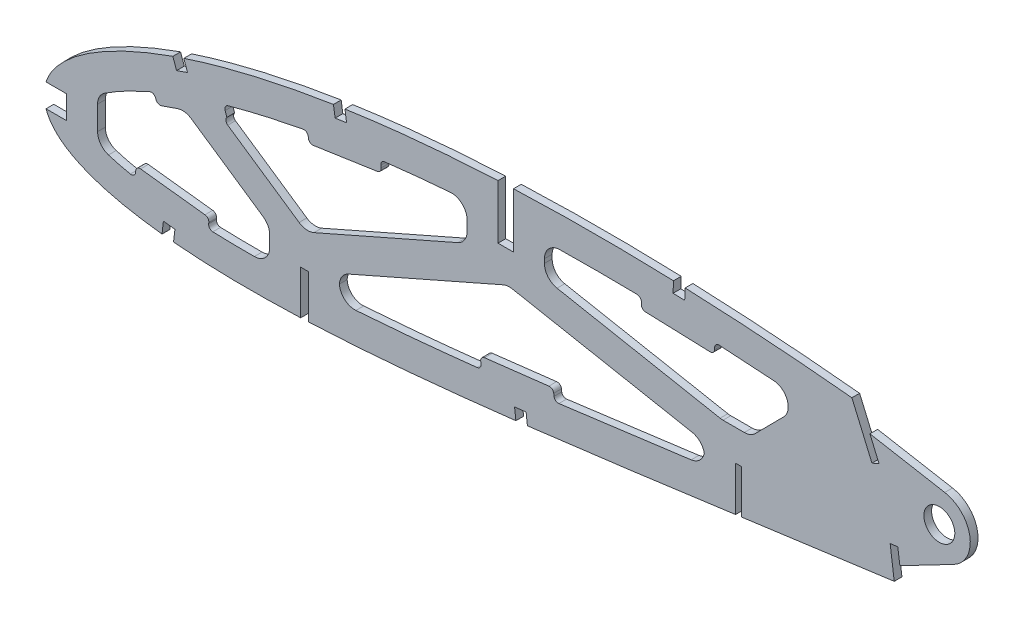
SolidWorks part; units mm, degrees
material "Pine"
ref_plane "Front Plane" through (0, 0, 0) normal (0, 0, 1) x (1, 0, 0)
ref_plane "Top Plane" through (0, 0, 0) normal (0, 1, 0) x (1, 0, 0)
ref_plane "Right Plane" through (0, 0, 0) normal (1, 0, 0) x (0, 0, -1)
curve "Curve2"
  spline degree 3 poles (520.229, 0.8111, 0) (520.1892, 0.8357, 0) (520.0299, 0.9341, 0) (519.6711, 1.1542, 0) (519.0735, 1.5208, 0) (518.237, 2.0313, 0) (517.1622, 2.6844, 0) (515.8486, 3.4756, 0) (514.2969, 4.4021, 0) (512.5075, 5.4598, 0) (510.4807, 6.6436, 0) (508.2172, 7.9486, 0) (505.7172, 9.3676, 0) (502.9816, 10.8948, 0) (500.0114, 12.5227, 0) (496.8072, 14.2443, 0) (493.3701, 16.0505, 0) (489.7015, 17.9338, 0) (485.8019, 19.8836, 0) (481.6733, 21.8919, 0) (477.317, 23.9487, 0) (472.7345, 26.0429, 0) (467.9284, 28.1661, 0) (462.9001, 30.305, 0) (457.6524, 32.4505, 0) (452.1876, 34.5902, 0) (446.5089, 36.7144, 0) (440.6184, 38.8094, 0) (434.5207, 40.866, 0) (428.2186, 42.8708, 0) (421.7166, 44.813, 0) (415.0186, 46.68, 0) (408.1302, 48.4622, 0) (401.0555, 50.1466, 0) (393.8008, 51.7219, 0) (386.3718, 53.1787, 0) (378.7746, 54.5024, 0) (371.0303, 55.692, 0) (363.2636, 56.6815, 0) (355.5128, 57.652, 0) (347.7736, 58.5637, 0) (339.9398, 59.4368, 0) (332.019, 60.2663, 0) (324.019, 61.0497, 0) (315.9478, 61.7836, 0) (307.814, 62.4658, 0) (299.6253, 63.0925, 0) (291.3904, 63.6628, 0) (283.1174, 64.1714, 0) (274.8152, 64.6183, 0) (266.4922, 65.0001, 0) (258.157, 65.3142, 0) (249.8185, 65.5589, 0) (241.4854, 65.7316, 0) (233.1666, 65.8314, 0) (224.8708, 65.8555, 0) (216.6071, 65.8035, 0) (208.384, 65.6736, 0) (200.2107, 65.464, 0) (192.0958, 65.1743, 0) (184.048, 64.8046, 0) (176.0762, 64.3519, 0) (168.189, 63.8191, 0) (160.3952, 63.2038, 0) (152.7034, 62.506, 0) (145.1216, 61.7286, 0) (137.6583, 60.8693, 0) (130.3214, 59.9308, 0) (123.1191, 58.9147, 0) (116.0593, 57.8206, 0) (109.1496, 56.6517, 0) (102.3976, 55.409, 0) (95.8102, 54.0963, 0) (89.3948, 52.714, 0) (83.1581, 51.266, 0) (77.1065, 49.7551, 0) (71.2467, 48.1838, 0) (65.5845, 46.5561, 0) (60.1256, 44.8756, 0) (54.8764, 43.1442, 0) (49.8409, 41.3683, 0) (45.0253, 39.5493, 0) (40.4333, 37.6928, 0) (36.0702, 35.8014, 0) (31.9393, 33.8806, 0) (28.0452, 31.9329, 0) (24.3908, 29.9636, 0) (20.9797, 27.9757, 0) (17.8153, 25.973, 0) (14.8987, 23.9604, 0) (12.2341, 21.9394, 0) (9.8224, 19.9149, 0) (7.6651, 17.8901, 0) (5.7652, 15.8664, 0) (4.1228, 13.8473, 0) (2.7399, 11.8344, 0) (1.6168, 9.8297, 0) (0.7561, 7.8345, 0) (0.1568, 5.85, 0) (-0.1712, 3.8792, 0) (-0.2528, 1.9205, 0) (-0.0842, 0.6392, 0) (0, 0, 0) knots 0 0 0 0 0.000254 0.001015 0.002283 0.004057 0.006331 0.009105 0.012374 0.016134 0.02038 0.025106 0.030306 0.035972 0.0421 0.048678 0.055702 0.06316 0.071046 0.07935 0.088063 0.097176 0.106678 0.116562 0.126814 0.137428 0.148394 0.1597 0.171338 0.183298 0.19557 0.208144 0.221012 0.234162 0.247587 0.261277 0.275223 0.289414 0.303771 0.317689 0.331784 0.34604 0.360444 0.374983 0.38964 0.404403 0.419257 0.434187 0.449177 0.464215 0.479284 0.49437 0.509458 0.524532 0.539579 0.554583 0.56953 0.584403 0.599191 0.613877 0.628447 0.642889 0.657186 0.671326 0.685294 0.699078 0.712665 0.726043 0.739198 0.752118 0.764792 0.777208 0.789356 0.801224 0.812804 0.824083 0.835055 0.84571 0.856038 0.866034 0.875689 0.884998 0.893953 0.902553 0.910789 0.918661 0.926166 0.933303 0.940071 0.946475 0.952518 0.958205 0.963547 0.968557 0.97325 0.977651 0.981787 0.985694 0.989415 0.993001 0.996508 1 1 1 1
curve "Curve3"
  spline degree 3 poles (0, 0, 0) (0.1336, -0.6306, 0) (0.4014, -1.8948, 0) (1.129, -3.7148, 0) (2.0912, -5.4642, 0) (3.3081, -7.1386, 0) (4.7718, -8.7374, 0) (6.479, -10.2623, 0) (8.428, -11.7125, 0) (10.6162, -13.0874, 0) (13.0406, -14.3883, 0) (15.6982, -15.6145, 0) (18.5868, -16.7656, 0) (21.7032, -17.8401, 0) (25.0435, -18.8396, 0) (28.6046, -19.7616, 0) (32.3825, -20.6074, 0) (36.3735, -21.375, 0) (40.5732, -22.065, 0) (44.9774, -22.6771, 0) (49.5814, -23.2117, 0) (54.3808, -23.6676, 0) (59.3708, -24.0458, 0) (64.5464, -24.3466, 0) (69.9027, -24.5709, 0) (75.4344, -24.718, 0) (81.1363, -24.7899, 0) (87.003, -24.788, 0) (93.0289, -24.7115, 0) (99.2088, -24.5648, 0) (105.5368, -24.3469, 0) (112.0073, -24.0604, 0) (118.6142, -23.7083, 0) (125.3518, -23.2917, 0) (132.2141, -22.8125, 0) (139.1951, -22.2745, 0) (146.2885, -21.679, 0) (153.4882, -21.0296, 0) (160.7876, -20.3295, 0) (168.1806, -19.5808, 0) (175.6606, -18.7872, 0) (183.2209, -17.9512, 0) (190.8551, -17.0772, 0) (198.5563, -16.1668, 0) (206.3179, -15.2253, 0) (214.1326, -14.2544, 0) (221.9939, -13.2579, 0) (229.8947, -12.2404, 0) (237.8276, -11.2019, 0) (245.786, -10.1497, 0) (253.7621, -9.0829, 0) (261.7491, -8.0072, 0) (269.7395, -6.9257, 0) (277.7256, -5.8389, 0) (285.7003, -4.7513, 0) (293.6562, -3.6657, 0) (301.5856, -2.5824, 0) (309.4812, -1.5067, 0) (317.3352, -0.4385, 0) (325.1402, 0.6201, 0) (332.8888, 1.6659, 0) (340.5737, 2.6975, 0) (348.187, 3.7144, 0) (355.721, 4.7168, 0) (363.0553, 5.6745, 0) (370.1707, 6.6383, 0) (377.0913, 7.4284, 0) (383.9258, 8.1028, 0) (390.6811, 8.6557, 0) (397.3493, 9.0951, 0) (403.9227, 9.4241, 0) (410.3934, 9.6473, 0) (416.7532, 9.7713, 0) (422.9943, 9.7993, 0) (429.1081, 9.7402, 0) (435.0867, 9.5987, 0) (440.9216, 9.3813, 0) (446.6049, 9.0952, 0) (452.1283, 8.7483, 0) (457.4837, 8.3456, 0) (462.6634, 7.8966, 0) (467.6597, 7.4078, 0) (472.4647, 6.8849, 0) (477.0715, 6.3387, 0) (481.4727, 5.7729, 0) (485.6616, 5.1968, 0) (489.6316, 4.6162, 0) (493.3764, 4.0385, 0) (496.89, 3.4693, 0) (500.1667, 2.916, 0) (503.2016, 2.384, 0) (505.9892, 1.8782, 0) (508.5257, 1.4052, 0) (510.8062, 0.9673, 0) (512.8275, 0.5717, 0) (514.5859, 0.2202, 0) (516.0789, -0.0824, 0) (517.3037, -0.3347, 0) (518.2586, -0.5328, 0) (518.9417, -0.6767, 0) (519.3522, -0.7624, 0) (519.5346, -0.8013, 0) (519.5802, -0.8111, 0) knots 0 0 0 0 0.003638 0.007293 0.011028 0.014901 0.018963 0.023258 0.027821 0.032679 0.037853 0.043362 0.049215 0.055422 0.061989 0.068918 0.076211 0.083868 0.091887 0.100266 0.109 0.118085 0.127515 0.137285 0.147388 0.157816 0.168563 0.179619 0.190977 0.202627 0.21456 0.226767 0.239236 0.251959 0.264924 0.27812 0.291536 0.30516 0.318981 0.332985 0.347163 0.361499 0.375981 0.390597 0.405333 0.420175 0.43511 0.450124 0.465203 0.480333 0.495501 0.51069 0.525887 0.541078 0.556247 0.571382 0.586466 0.601485 0.616424 0.631269 0.646007 0.660621 0.675098 0.689423 0.703582 0.716908 0.730009 0.742952 0.755726 0.76832 0.780724 0.792927 0.804916 0.816679 0.828204 0.839475 0.850481 0.861208 0.871639 0.881763 0.891564 0.901027 0.910139 0.918884 0.927249 0.935221 0.942785 0.949928 0.956638 0.962904 0.968712 0.974054 0.978918 0.983297 0.98718 0.990561 0.993433 0.995791 0.99763 0.998946 0.999737 1 1 1 1
sketch "Sketch1" plane through (0, 0, 0) normal (0, 0, 1) x (1, 0, 0)
  line L1 (519.5802, -0.8111) -> (524.4049, -1.7687)
  line L2 (520.229, 0.8111) -> (524.4049, -1.7687)
  spline S0 degree 3 poles (-2903.7635, -749.124) (66.2436, 68.8235) (-8.6937, 20.855) (1.129, -3.7148) (2.0912, -5.4642) (3.3081, -7.1386) (4.7718, -8.7374) (6.479, -10.2623) (8.428, -11.7125) (10.6162, -13.0874) (13.0406, -14.3883) (15.6982, -15.6145) (18.5868, -16.7656) (21.7032, -17.8401) (25.0435, -18.8396) (28.6046, -19.7616) (32.3825, -20.6074) (36.3735, -21.375) (40.5732, -22.065) (44.9774, -22.6771) (49.5814, -23.2117) (54.3808, -23.6676) (59.3708, -24.0458) (64.5464, -24.3466) (69.9027, -24.5709) (75.4344, -24.718) (81.1363, -24.7899) (87.003, -24.788) (93.0289, -24.7115) (99.2088, -24.5648) (105.5368, -24.3469) (112.0073, -24.0604) (118.6142, -23.7083) (125.3518, -23.2917) (132.2141, -22.8125) (139.1951, -22.2745) (146.2885, -21.679) (153.4882, -21.0296) (160.7876, -20.3295) (168.1806, -19.5808) (175.6606, -18.7872) (183.2209, -17.9512) (190.8551, -17.0772) (198.5563, -16.1668) (206.3179, -15.2253) (214.1326, -14.2544) (221.9939, -13.2579) (229.8947, -12.2404) (237.8276, -11.2019) (245.786, -10.1497) (253.7621, -9.0829) (261.7491, -8.0072) (269.7395, -6.9257) (277.7256, -5.8389) (285.7003, -4.7513) (293.6562, -3.6657) (301.5856, -2.5824) (309.4812, -1.5067) (317.3352, -0.4385) (325.1402, 0.6201) (332.8888, 1.6659) (340.5737, 2.6975) (348.187, 3.7144) (355.721, 4.7168) (363.0553, 5.6745) (370.1707, 6.6383) (377.0913, 7.4284) (383.9258, 8.1028) (390.6811, 8.6557) (397.3493, 9.0951) (403.9227, 9.4241) (410.3934, 9.6473) (416.7532, 9.7713) (422.9943, 9.7993) (429.1081, 9.7402) (435.0867, 9.5987) (440.9216, 9.3813) (446.6049, 9.0952) (452.1283, 8.7483) (457.4837, 8.3456) (462.6634, 7.8966) (467.6597, 7.4078) (472.4647, 6.8849) (477.0715, 6.3387) (481.4727, 5.7729) (485.6616, 5.1968) (489.6316, 4.6162) (493.3764, 4.0385) (496.89, 3.4693) (500.1667, 2.916) (503.2016, 2.384) (505.9892, 1.8782) (508.5257, 1.4052) (510.8062, 0.9673) (512.8275, 0.5717) (514.5859, 0.2202) (516.0789, -0.0824) (517.3037, -0.3347) (518.2586, -0.5328) (518.9417, -0.6767) (537.0698, -4.4604) (553.3394, -15.9066) (1193.1482, 2921.6684) knots -0.137857 -0.137857 -0.137857 -0.137857 0.003638 0.007293 0.011028 0.014901 0.018963 0.023258 0.027821 0.032679 0.037853 0.043362 0.049215 0.055422 0.061989 0.068918 0.076211 0.083868 0.091887 0.100266 0.109 0.118085 0.127515 0.137285 0.147388 0.157816 0.168563 0.179619 0.190977 0.202627 0.21456 0.226767 0.239236 0.251959 0.264924 0.27812 0.291536 0.30516 0.318981 0.332985 0.347163 0.361499 0.375981 0.390597 0.405333 0.420175 0.43511 0.450124 0.465203 0.480333 0.495501 0.51069 0.525887 0.541078 0.556247 0.571382 0.586466 0.601485 0.616424 0.631269 0.646007 0.660621 0.675098 0.689423 0.703582 0.716908 0.730009 0.742952 0.755726 0.76832 0.780724 0.792927 0.804916 0.816679 0.828204 0.839475 0.850481 0.861208 0.871639 0.881763 0.891564 0.901027 0.910139 0.918884 0.927249 0.935221 0.942785 0.949928 0.956638 0.962904 0.968712 0.974054 0.978918 0.983297 0.98718 0.990561 0.993433 0.995791 0.99763 0.998946 0.999737 1.102307 1.102307 1.102307 1.102307 only from (0, 0) to (519.5802, -0.8111) construction
  spline S1 degree 3 poles (2144.5607, 2521.6799) (550.9976, -26.3511) (537.2872, -9.6513) (519.6711, 1.1542) (519.0735, 1.5208) (518.237, 2.0313) (517.1622, 2.6844) (515.8486, 3.4756) (514.2969, 4.4021) (512.5075, 5.4598) (510.4807, 6.6436) (508.2172, 7.9486) (505.7172, 9.3676) (502.9816, 10.8948) (500.0114, 12.5227) (496.8072, 14.2443) (493.3701, 16.0505) (489.7015, 17.9338) (485.8019, 19.8836) (481.6733, 21.8919) (477.317, 23.9487) (472.7345, 26.0429) (467.9284, 28.1661) (462.9001, 30.305) (457.6524, 32.4505) (452.1876, 34.5902) (446.5089, 36.7144) (440.6184, 38.8094) (434.5207, 40.866) (428.2186, 42.8708) (421.7166, 44.813) (415.0186, 46.68) (408.1302, 48.4622) (401.0555, 50.1466) (393.8008, 51.7219) (386.3718, 53.1787) (378.7746, 54.5024) (371.0303, 55.692) (363.2636, 56.6815) (355.5128, 57.652) (347.7736, 58.5637) (339.9398, 59.4368) (332.019, 60.2663) (324.019, 61.0497) (315.9478, 61.7836) (307.814, 62.4658) (299.6253, 63.0925) (291.3904, 63.6628) (283.1174, 64.1714) (274.8152, 64.6183) (266.4922, 65.0001) (258.157, 65.3142) (249.8185, 65.5589) (241.4854, 65.7316) (233.1666, 65.8314) (224.8708, 65.8555) (216.6071, 65.8035) (208.384, 65.6736) (200.2107, 65.464) (192.0958, 65.1743) (184.048, 64.8046) (176.0762, 64.3519) (168.189, 63.8191) (160.3952, 63.2038) (152.7034, 62.506) (145.1216, 61.7286) (137.6583, 60.8693) (130.3214, 59.9308) (123.1191, 58.9147) (116.0593, 57.8206) (109.1496, 56.6517) (102.3976, 55.409) (95.8102, 54.0963) (89.3948, 52.714) (83.1581, 51.266) (77.1065, 49.7551) (71.2467, 48.1838) (65.5845, 46.5561) (60.1256, 44.8756) (54.8764, 43.1442) (49.8409, 41.3683) (45.0253, 39.5493) (40.4333, 37.6928) (36.0702, 35.8014) (31.9393, 33.8806) (28.0452, 31.9329) (24.3908, 29.9636) (20.9797, 27.9757) (17.8153, 25.973) (14.8987, 23.9604) (12.2341, 21.9394) (9.8224, 19.9149) (7.6651, 17.8901) (5.7652, 15.8664) (4.1228, 13.8473) (2.7399, 11.8344) (1.6168, 9.8297) (0.7561, 7.8345) (0.1568, 5.85) (-0.1712, 3.8792) (-1.2714, -22.5145) (85.5395, -42.7616) (-2987.8188, -259.5241) knots -0.109813 -0.109813 -0.109813 -0.109813 0.000254 0.001015 0.002283 0.004057 0.006331 0.009105 0.012374 0.016134 0.02038 0.025106 0.030306 0.035972 0.0421 0.048678 0.055702 0.06316 0.071046 0.07935 0.088063 0.097176 0.106678 0.116562 0.126814 0.137428 0.148394 0.1597 0.171338 0.183298 0.19557 0.208144 0.221012 0.234162 0.247587 0.261277 0.275223 0.289414 0.303771 0.317689 0.331784 0.34604 0.360444 0.374983 0.38964 0.404403 0.419257 0.434187 0.449177 0.464215 0.479284 0.49437 0.509458 0.524532 0.539579 0.554583 0.56953 0.584403 0.599191 0.613877 0.628447 0.642889 0.657186 0.671326 0.685294 0.699078 0.712665 0.726043 0.739198 0.752118 0.764792 0.777208 0.789356 0.801224 0.812804 0.824083 0.835055 0.84571 0.856038 0.866034 0.875689 0.884998 0.893953 0.902553 0.910789 0.918661 0.926166 0.933303 0.940071 0.946475 0.952518 0.958205 0.963547 0.968557 0.97325 0.977651 0.981787 0.985694 0.989415 0.993001 0.996508 1.132043 1.132043 1.132043 1.132043 only from (520.229, 0.8111) to (0, 0) construction
  spline S2 degree 3 poles (0, 0) (0.1336, -0.6306) (0.4014, -1.8948) (1.129, -3.7148) (2.0912, -5.4642) (3.3081, -7.1386) (4.7718, -8.7374) (6.479, -10.2623) (8.428, -11.7125) (10.6162, -13.0874) (13.0406, -14.3883) (15.6982, -15.6145) (18.5868, -16.7656) (21.7032, -17.8401) (25.0435, -18.8396) (28.6046, -19.7616) (32.3825, -20.6074) (36.3735, -21.375) (40.5732, -22.065) (44.9774, -22.6771) (49.5814, -23.2117) (54.3808, -23.6676) (59.3708, -24.0458) (64.5464, -24.3466) (69.9027, -24.5709) (75.4344, -24.718) (81.1363, -24.7899) (87.003, -24.788) (93.0289, -24.7115) (99.2088, -24.5648) (105.5368, -24.3469) (112.0073, -24.0604) (118.6142, -23.7083) (125.3518, -23.2917) (132.2141, -22.8125) (139.1951, -22.2745) (146.2885, -21.679) (153.4882, -21.0296) (160.7876, -20.3295) (168.1806, -19.5808) (175.6606, -18.7872) (183.2209, -17.9512) (190.8551, -17.0772) (198.5563, -16.1668) (206.3179, -15.2253) (214.1326, -14.2544) (221.9939, -13.2579) (229.8947, -12.2404) (237.8276, -11.2019) (245.786, -10.1497) (253.7621, -9.0829) (261.7491, -8.0072) (269.7395, -6.9257) (277.7256, -5.8389) (285.7003, -4.7513) (293.6562, -3.6657) (301.5856, -2.5824) (309.4812, -1.5067) (317.3352, -0.4385) (325.1402, 0.6201) (332.8888, 1.6659) (340.5737, 2.6975) (348.187, 3.7144) (355.721, 4.7168) (363.0553, 5.6745) (370.1707, 6.6383) (377.0913, 7.4284) (383.9258, 8.1028) (390.6811, 8.6557) (397.3493, 9.0951) (403.9227, 9.4241) (410.3934, 9.6473) (416.7532, 9.7713) (422.9943, 9.7993) (429.1081, 9.7402) (435.0867, 9.5987) (440.9216, 9.3813) (446.6049, 9.0952) (452.1283, 8.7483) (457.4837, 8.3456) (462.6634, 7.8966) (467.6597, 7.4078) (472.4647, 6.8849) (477.0715, 6.3387) (481.4727, 5.7729) (485.6616, 5.1968) (489.6316, 4.6162) (493.3764, 4.0385) (496.89, 3.4693) (500.1667, 2.916) (503.2016, 2.384) (505.9892, 1.8782) (508.5257, 1.4052) (510.8062, 0.9673) (512.8275, 0.5717) (514.5859, 0.2202) (516.0789, -0.0824) (517.3037, -0.3347) (518.2586, -0.5328) (518.9417, -0.6767) (519.3522, -0.7624) (519.5346, -0.8013) (519.5802, -0.8111) knots 0 0 0 0 0.003638 0.007293 0.011028 0.014901 0.018963 0.023258 0.027821 0.032679 0.037853 0.043362 0.049215 0.055422 0.061989 0.068918 0.076211 0.083868 0.091887 0.100266 0.109 0.118085 0.127515 0.137285 0.147388 0.157816 0.168563 0.179619 0.190977 0.202627 0.21456 0.226767 0.239236 0.251959 0.264924 0.27812 0.291536 0.30516 0.318981 0.332985 0.347163 0.361499 0.375981 0.390597 0.405333 0.420175 0.43511 0.450124 0.465203 0.480333 0.495501 0.51069 0.525887 0.541078 0.556247 0.571382 0.586466 0.601485 0.616424 0.631269 0.646007 0.660621 0.675098 0.689423 0.703582 0.716908 0.730009 0.742952 0.755726 0.76832 0.780724 0.792927 0.804916 0.816679 0.828204 0.839475 0.850481 0.861208 0.871639 0.881763 0.891564 0.901027 0.910139 0.918884 0.927249 0.935221 0.942785 0.949928 0.956638 0.962904 0.968712 0.974054 0.978918 0.983297 0.98718 0.990561 0.993433 0.995791 0.99763 0.998946 0.999737 1 1 1 1
  spline S3 degree 3 poles (520.229, 0.8111) (520.1892, 0.8357) (520.0299, 0.9341) (519.6711, 1.1542) (519.0735, 1.5208) (518.237, 2.0313) (517.1622, 2.6844) (515.8486, 3.4756) (514.2969, 4.4021) (512.5075, 5.4598) (510.4807, 6.6436) (508.2172, 7.9486) (505.7172, 9.3676) (502.9816, 10.8948) (500.0114, 12.5227) (496.8072, 14.2443) (493.3701, 16.0505) (489.7015, 17.9338) (485.8019, 19.8836) (481.6733, 21.8919) (477.317, 23.9487) (472.7345, 26.0429) (467.9284, 28.1661) (462.9001, 30.305) (457.6524, 32.4505) (452.1876, 34.5902) (446.5089, 36.7144) (440.6184, 38.8094) (434.5207, 40.866) (428.2186, 42.8708) (421.7166, 44.813) (415.0186, 46.68) (408.1302, 48.4622) (401.0555, 50.1466) (393.8008, 51.7219) (386.3718, 53.1787) (378.7746, 54.5024) (371.0303, 55.692) (363.2636, 56.6815) (355.5128, 57.652) (347.7736, 58.5637) (339.9398, 59.4368) (332.019, 60.2663) (324.019, 61.0497) (315.9478, 61.7836) (307.814, 62.4658) (299.6253, 63.0925) (291.3904, 63.6628) (283.1174, 64.1714) (274.8152, 64.6183) (266.4922, 65.0001) (258.157, 65.3142) (249.8185, 65.5589) (241.4854, 65.7316) (233.1666, 65.8314) (224.8708, 65.8555) (216.6071, 65.8035) (208.384, 65.6736) (200.2107, 65.464) (192.0958, 65.1743) (184.048, 64.8046) (176.0762, 64.3519) (168.189, 63.8191) (160.3952, 63.2038) (152.7034, 62.506) (145.1216, 61.7286) (137.6583, 60.8693) (130.3214, 59.9308) (123.1191, 58.9147) (116.0593, 57.8206) (109.1496, 56.6517) (102.3976, 55.409) (95.8102, 54.0963) (89.3948, 52.714) (83.1581, 51.266) (77.1065, 49.7551) (71.2467, 48.1838) (65.5845, 46.5561) (60.1256, 44.8756) (54.8764, 43.1442) (49.8409, 41.3683) (45.0253, 39.5493) (40.4333, 37.6928) (36.0702, 35.8014) (31.9393, 33.8806) (28.0452, 31.9329) (24.3908, 29.9636) (20.9797, 27.9757) (17.8153, 25.973) (14.8987, 23.9604) (12.2341, 21.9394) (9.8224, 19.9149) (7.6651, 17.8901) (5.7652, 15.8664) (4.1228, 13.8473) (2.7399, 11.8344) (1.6168, 9.8297) (0.7561, 7.8345) (0.1568, 5.85) (-0.1712, 3.8792) (-0.2528, 1.9205) (-0.0842, 0.6392) (0, 0) knots 0 0 0 0 0.000254 0.001015 0.002283 0.004057 0.006331 0.009105 0.012374 0.016134 0.02038 0.025106 0.030306 0.035972 0.0421 0.048678 0.055702 0.06316 0.071046 0.07935 0.088063 0.097176 0.106678 0.116562 0.126814 0.137428 0.148394 0.1597 0.171338 0.183298 0.19557 0.208144 0.221012 0.234162 0.247587 0.261277 0.275223 0.289414 0.303771 0.317689 0.331784 0.34604 0.360444 0.374983 0.38964 0.404403 0.419257 0.434187 0.449177 0.464215 0.479284 0.49437 0.509458 0.524532 0.539579 0.554583 0.56953 0.584403 0.599191 0.613877 0.628447 0.642889 0.657186 0.671326 0.685294 0.699078 0.712665 0.726043 0.739198 0.752118 0.764792 0.777208 0.789356 0.801224 0.812804 0.824083 0.835055 0.84571 0.856038 0.866034 0.875689 0.884998 0.893953 0.902553 0.910789 0.918661 0.926166 0.933303 0.940071 0.946475 0.952518 0.958205 0.963547 0.968557 0.97325 0.977651 0.981787 0.985694 0.989415 0.993001 0.996508 1 1 1 1
extrude "Boss-Extrude1" add sketch "Sketch1" along normal blind 3.175
sketch "Sketch2" plane through (0, 0, 0) normal (0, 0, -1) x (-1, 0, 0)
  line L2 (-286.0676, 13.2177) -> (-286.0676, -4.8021)
  line L7 (-192.4051, 65.2789) -> (-192.4051, 42.658)
  line L10 (-108.2676, -6.3385) -> (-108.2676, -24.0465)
  line L14 (-283.5276, 13.2177) -> (-283.5276, -4.8021)
  line L19 (-186.0551, 65.2789) -> (-186.0551, 42.658)
  line L22 (-105.0926, -6.3385) -> (-105.0926, -24.0465)
  line L24 (-286.0676, -4.8021) -> (-286.0676, -8.3904)
  line L25 (-286.0676, -8.3904) -> (-283.5276, -6.5962)
  line L26 (-283.5276, -6.5962) -> (-283.5276, -4.8021)
  line L27 (-192.4051, 65.2789) -> (-192.4051, 74.5745)
  line L28 (-192.4051, 74.5745) -> (-186.0551, 68.2245)
  line L29 (-186.0551, 68.2245) -> (-186.0551, 65.2789)
  line L30 (-108.2676, -24.0465) -> (-108.2676, -27.6366)
  line L31 (-108.2676, -27.6366) -> (-105.0926, -25.3939)
  line L32 (-105.0926, -25.3939) -> (-105.0926, -24.0465)
  line L33 (-108.2676, -6.3385) -> (-105.0926, -6.3385)
  line L34 (-192.4051, 42.658) -> (-186.0551, 42.658)
  line L35 (-286.0676, 13.2177) -> (-283.5276, 13.2177)
extrude "Cut-Extrude2" cut sketch "Sketch2" against normal blind 7.62
sketch "Sketch4" plane through (0, 0, 0) normal (0, 0, -1) x (-1, 0, 0)
  circle A1 centre (-367.1422, 33.2326) radius 6.35
extrude "Cut-Extrude3" cut sketch "Sketch4" against normal blind 7.62
sketch "Sketch5" plane through (0, 0, 0) normal (0, 0, -1) x (-1, 0, 0)
  line L0 (-348.2218, 35.451) -> (-350.8885, 58.1944) construction
  line L1 (-350.8885, 58.1944) -> (-391.6719, 53.4125) construction
  line L2 (-348.2581, 30.7238) -> (-350.9465, 10.4871) construction
  line L3 (-351.7828, 4.1924) -> (-398.5601, 10.4067) construction
  line L4 (-367.1422, 33.2326) -> (-348.2218, 35.451) construction
  line L5 (-367.1422, 33.2326) -> (-349.6474, 25.6936) construction
  line L6 (-349.6474, 25.6936) -> (-338.6489, 51.2166) construction
  line L7 (-338.6489, 51.2166) -> (-342.4184, 42.4692)
  line L9 (-342.4184, 42.4692) -> (-339.5026, 41.2127)
  line L10 (-331.9636, 58.7075) -> (-339.5026, 41.2127)
  line L11 (-350.9465, 10.4871) -> (-350.1103, 16.7818)
  line L13 (-350.1103, 16.7818) -> (-346.9629, 16.3637)
  line L14 (-348.6354, 3.7743) -> (-346.9629, 16.3637)
  line L15 (-373.0051, 21.9669) -> (-350.9465, 10.4871)
  line L16 (-369.3728, 45.7352) -> (-338.6489, 51.2166)
  line L17 (-331.9636, 58.7075) -> (-329.4445, 64.5532)
  line L18 (-329.4445, 64.5532) -> (-547.4475, 21.9669)
  line L19 (-547.4475, 21.9669) -> (-524.2073, -22.3113)
  line L20 (-524.2073, -22.3113) -> (-348.6354, 3.7743)
  circle A2 centre (-367.1422, 33.2326) radius 19.05
  circle A3 centre (-367.1422, 33.2326) radius 19.05 construction
  circle A4 centre (-367.1422, 33.2326) radius 12.7
  arc A5 (-369.3728, 45.7352) -> (-373.0051, 21.9669) centre (-367.1422, 33.2326) ccw
  spline S0 degree 3 poles (-520.229, 0.8111) (-520.1892, 0.8357) (-520.0299, 0.9341) (-519.6711, 1.1542) (-519.0735, 1.5208) (-518.237, 2.0313) (-517.1622, 2.6844) (-515.8486, 3.4756) (-514.2969, 4.4021) (-512.5075, 5.4598) (-510.4807, 6.6436) (-508.2172, 7.9486) (-505.7172, 9.3676) (-502.9816, 10.8948) (-500.0114, 12.5227) (-496.8072, 14.2443) (-493.3701, 16.0505) (-489.7015, 17.9338) (-485.8019, 19.8836) (-481.6733, 21.8919) (-477.317, 23.9487) (-472.7345, 26.0429) (-467.9284, 28.1661) (-462.9001, 30.305) (-457.6524, 32.4505) (-452.1876, 34.5902) (-446.5089, 36.7144) (-440.6184, 38.8094) (-434.5207, 40.866) (-428.2186, 42.8708) (-421.7166, 44.813) (-415.0186, 46.68) (-408.1302, 48.4622) (-401.0555, 50.1466) (-393.8008, 51.7219) (-386.3718, 53.1787) (-378.7746, 54.5024) (-371.0303, 55.692) (-363.2636, 56.6815) (-355.5128, 57.652) (-347.7736, 58.5637) (-339.9398, 59.4368) (-332.019, 60.2663) (-324.019, 61.0497) (-315.9478, 61.7836) (-307.814, 62.4658) (-299.6253, 63.0925) (-291.3904, 63.6628) (-283.1174, 64.1714) (-274.8152, 64.6183) (-266.4922, 65.0001) (-258.157, 65.3142) (-249.8185, 65.5589) (-241.4854, 65.7316) (-233.1666, 65.8314) (-224.8708, 65.8555) (-216.6071, 65.8035) (-208.384, 65.6736) (-200.3208, 65.4668) (-195.0004, 65.2779) (-192.4051, 65.1731) knots 0 0 0 0 0.000254 0.001015 0.002283 0.004057 0.006331 0.009105 0.012374 0.016134 0.02038 0.025106 0.030306 0.035972 0.0421 0.048678 0.055702 0.06316 0.071046 0.07935 0.088063 0.097176 0.106678 0.116562 0.126814 0.137428 0.148394 0.1597 0.171338 0.183298 0.19557 0.208144 0.221012 0.234162 0.247587 0.261277 0.275223 0.289414 0.303771 0.317689 0.331784 0.34604 0.360444 0.374983 0.38964 0.404403 0.419257 0.434187 0.449177 0.464215 0.479284 0.49437 0.509458 0.524532 0.539579 0.554583 0.56953 0.584403 0.599191 0.61328 0.61328 0.61328 0.61328 construction
  spline S1 degree 3 poles (-286.0676, -4.7011) (-288.6001, -4.3556) (-293.7767, -3.6493) (-301.5856, -2.5824) (-309.4812, -1.5067) (-317.3352, -0.4385) (-325.1402, 0.6201) (-332.8888, 1.6659) (-340.5737, 2.6975) (-348.187, 3.7144) (-355.721, 4.7168) (-363.0553, 5.6745) (-370.1707, 6.6383) (-377.0913, 7.4284) (-383.9258, 8.1028) (-390.6811, 8.6557) (-397.3493, 9.0951) (-403.9227, 9.4241) (-410.3934, 9.6473) (-416.7532, 9.7713) (-422.9943, 9.7993) (-429.1081, 9.7402) (-435.0867, 9.5987) (-440.9216, 9.3813) (-446.6049, 9.0952) (-452.1283, 8.7483) (-457.4837, 8.3456) (-462.6634, 7.8966) (-467.6597, 7.4078) (-472.4647, 6.8849) (-477.0715, 6.3387) (-481.4727, 5.7729) (-485.6616, 5.1968) (-489.6316, 4.6162) (-493.3764, 4.0385) (-496.89, 3.4693) (-500.1667, 2.916) (-503.2016, 2.384) (-505.9892, 1.8782) (-508.5257, 1.4052) (-510.8062, 0.9673) (-512.8275, 0.5717) (-514.5859, 0.2202) (-516.0789, -0.0824) (-517.3037, -0.3347) (-518.2586, -0.5328) (-518.9417, -0.6767) (-519.3522, -0.7624) (-519.5346, -0.8013) (-519.5802, -0.8111) knots 0.556934 0.556934 0.556934 0.556934 0.571382 0.586466 0.601485 0.616424 0.631269 0.646007 0.660621 0.675098 0.689423 0.703582 0.716908 0.730009 0.742952 0.755726 0.76832 0.780724 0.792927 0.804916 0.816679 0.828204 0.839475 0.850481 0.861208 0.871639 0.881763 0.891564 0.901027 0.910139 0.918884 0.927249 0.935221 0.942785 0.949928 0.956638 0.962904 0.968712 0.974054 0.978918 0.983297 0.98718 0.990561 0.993433 0.995791 0.99763 0.998946 0.999737 1 1 1 1 construction
  dimension "D2" = 30
  dimension "D3" = 19.05
  dimension "D4" = 3.175
  dimension "D5" = 3.175
  dimension "D6" = 12.7
  dimension "D1" = 12.7
  dimension "D7" = 6.35
extrude "Cut-Extrude4" cut sketch "Sketch5" against normal blind 7.62
sketch "Sketch6" plane through (0, 0, 3.175) normal (0, 0, 1) x (1, 0, 0)
  line L1 (9.0491, -2.3116) -> (9.0491, 7.2134)
  line L2 (48.2015, -22.9304) -> (48.143, -23.4415)
  line L3 (-0.4759, 7.2134) -> (9.0491, 7.2134)
  line L4 (52.9259, -23.471) -> (52.8674, -23.9821)
  line L5 (58.6444, 39.5788) -> (57.0937, 44.0456)
  line L6 (48.143, -23.4415) -> (52.8674, -23.9821)
  line L7 (53.4849, -18.7224) -> (48.7591, -18.1683)
  line L9 (52.9259, -23.471) -> (53.4849, -18.7224)
  line L11 (123.9218, 54.3657) -> (123.2199, 59.0934)
  line L13 (198.1367, -16.3203) -> (197.5795, -11.5893)
  line L15 (197.5795, -11.5893) -> (192.8497, -12.1463)
  line L17 (262.6616, 60.6229) -> (262.8439, 65.3728)
  line L19 (257.9021, 60.7874) -> (262.6616, 60.6229)
  line L21 (258.0615, 65.5447) -> (257.9021, 60.7874)
  line L23 (192.8497, -12.1463) -> (193.4048, -16.8803)
  line L25 (119.2109, 53.6664) -> (123.9218, 54.3657)
  line L27 (118.502, 58.3704) -> (119.2109, 53.6664)
  line L29 (48.7591, -18.1683) -> (48.2015, -22.9304)
  line L31 (54.1454, 38.0169) -> (58.6444, 39.5788)
  line L33 (52.5867, 42.5063) -> (54.1454, 38.0169)
  line L35 (-0.4759, -2.3116) -> (9.0491, -2.3116)
  line L37 (-0.4759, -2.3116) -> (-0.4759, 7.2134)
  arc A1 (123.2199, 59.0934) -> (118.502, 58.3704) centre (443.7447, -2048.1229) ccw
  arc A3 (262.8439, 65.3728) -> (258.0615, 65.5447) centre (100.7832, -4376.4516) ccw
  arc A5 (193.4048, -16.8803) -> (198.1367, -16.3203) centre (-903.0921, 9268.763) ccw
  spline S1 degree 3 poles (57.0937, 44.0456) (56.342, 43.7907) (54.8391, 43.2792) (53.3372, 42.7645) (52.5867, 42.5063) knots 0 0 0 0 0.5 1 1 1 1
extrude "Cut-Extrude5" cut sketch "Sketch6" against normal blind 7.62
sketch "Sketch7" plane through (0, 0, 3.175) normal (0, 0, 1) x (1, 0, 0)
  line L0 (57.545, 25.7536) -> (52.3119, 23.9368)
  line L1 (92.3926, -12.01) -> (92.3926, 6.3615) construction
  line L2 (92.3926, 6.3615) -> (114.6176, 6.3615) construction
  line L3 (107.3436, 7.2399) -> (173.3551, 36.2646)
  line L4 (173.3551, 36.308) -> (173.3551, 51.4354)
  line L5 (137.6967, 48.0627) -> (138.349, 43.6684)
  line L6 (138.349, 43.6684) -> (108.5412, 39.2432)
  line L7 (108.5412, 39.2432) -> (107.899, 43.5043)
  line L8 (73.4693, 35.5995) -> (74.8069, 31.7464)
  line L9 (74.8069, 31.7464) -> (72.4953, 30.9439)
  line L10 (173.3551, 36.308) -> (173.3551, 36.2646)
  line L11 (72.4953, 30.9439) -> (107.3436, 7.2399)
  line L12 (107.3436, 7.2399) -> (186.6743, 42.1209) construction
  line L13 (62.0489, 38.0496) -> (107.3436, 7.2399) construction
  line L14 (74.8069, 31.7464) -> (52.3119, 23.9368) construction
  line L15 (120.9676, -0.6431) -> (120.9676, -10.8361)
  line L16 (120.9676, 6.3615) -> (120.9676, 6.2936)
  line L17 (179.2958, -5.6062) -> (178.7578, -1.0182)
  line L18 (178.7578, -1.0182) -> (208.7069, 2.509)
  line L19 (208.7069, 2.509) -> (209.2454, -2.0631)
  line L20 (270.8276, 6.0397) -> (270.8276, 14.3124)
  line L21 (189.9804, 29.7012) -> (270.8276, 14.3124)
  line L22 (188.0428, 30.07) -> (270.8276, 14.3124) construction
  line L23 (120.9676, 6.3615) -> (120.9676, -10.8361) construction
  line L24 (120.9676, -0.6431) -> (189.9804, 29.7012)
  line L25 (205.1051, 39.7503) -> (277.7766, 25.9177)
  line L26 (277.7766, 25.9177) -> (289.7701, 25.9177)
  line L27 (289.7701, 25.9177) -> (312.9255, 49.2886)
  line L28 (275.0355, 51.8803) -> (274.8672, 47.4932)
  line L29 (274.8672, 47.4932) -> (244.7845, 48.5334)
  line L30 (244.7845, 48.5334) -> (244.9326, 52.9544)
  line L31 (205.1051, 52.8817) -> (205.1051, 39.7503)
  line L32 (190.4175, 42.546) -> (277.7766, 25.9177) construction
  line L33 (205.1051, 52.8817) -> (205.1051, 36.308) construction
  line L38 (292.4176, 19.5677) -> (326.9124, 54.3836) construction
  line L39 (58.4775, 32.7991) -> (106.6801, 0.0115) construction
  line L40 (106.6801, 0.0115) -> (189.2301, 36.308) construction
  line L41 (189.2301, 36.308) -> (277.1776, 19.5677) construction
  line L43 (46.3133, 21.8543) -> (44.9462, 25.7917)
  line L44 (21.7491, 13.2042) -> (21.7491, 13.2042)
  line L45 (21.7491, 13.2042) -> (21.7491, -4.3475)
  line L46 (37.0956, -8.5758) -> (37.6226, -4.0756)
  line L47 (37.6226, -4.0756) -> (67.5835, -7.5883)
  line L48 (67.5835, -7.5883) -> (67.0949, -11.7384)
  line L49 (92.3926, -12.01) -> (92.3926, 2.0501)
  line L51 (57.545, 25.7536) -> (92.3926, 2.0501)
  line L52 (54.9061, 27.5486) -> (103.1087, -5.239) construction
  line L53 (57.545, 25.7536) -> (46.3133, 21.8543)
  line L54 (68.8082, 29.6638) -> (46.3133, 21.8543) construction
  line L76 (15.3991, 13.5634) -> (15.3991, -8.4331)
  line L77 (42.6276, -15.932) -> (43.1909, -11.1219)
  line L78 (43.1909, -11.1219) -> (60.5342, -13.1553)
  line L79 (60.5342, -13.1553) -> (59.9982, -17.7085)
  line L80 (98.7426, -18.2144) -> (98.7426, 0.0115)
  line L81 (98.7426, 0.0115) -> (114.6176, 0.0115)
  line L82 (114.6176, 0.0115) -> (114.6176, -17.5598)
  line L83 (186.3453, -11.2008) -> (185.8037, -6.5822)
  line L84 (185.8037, -6.5822) -> (203.1432, -4.5402)
  line L85 (203.1432, -4.5402) -> (203.6857, -9.1463)
  line L86 (277.1776, 0.4955) -> (277.1776, 19.5677)
  line L87 (277.1776, 19.5677) -> (292.4176, 19.5677)
  line L88 (292.4176, 19.5677) -> (292.4176, 2.5743)
  line L89 (341.5051, 9.2279) -> (339.832, 21.8221)
  line L90 (339.832, 21.8221) -> (355.5688, 23.9127)
  line L91 (355.5688, 23.9127) -> (356.0486, 20.3008)
  line L92 (356.0486, 20.3008) -> (370.0737, 27.5997)
  line L93 (368.2575, 39.4839) -> (349.1504, 42.8928)
  line L94 (349.1504, 42.8928) -> (350.7629, 39.1506)
  line L95 (350.7629, 39.1506) -> (336.184, 32.8681)
  line L96 (336.184, 32.8681) -> (326.9124, 54.3836)
  line L97 (268.9359, 58.5274) -> (268.7644, 54.058)
  line L98 (268.7644, 54.058) -> (251.3433, 54.6604)
  line L99 (251.3433, 54.6604) -> (251.4937, 59.1512)
  line L100 (198.7551, 59.051) -> (198.7551, 36.308)
  line L101 (198.7551, 36.308) -> (179.7051, 36.308)
  line L102 (179.7051, 36.308) -> (179.7051, 58.1939)
  line L103 (130.4659, 53.5267) -> (131.1354, 49.0171)
  line L104 (131.1354, 49.0171) -> (113.876, 46.4548)
  line L105 (113.876, 46.4548) -> (113.2071, 50.8935)
  line L106 (65.2844, 39.8142) -> (66.7256, 35.6626)
  line L107 (66.7256, 35.6626) -> (50.2293, 29.9356)
  line L108 (50.2293, 29.9356) -> (48.7609, 34.165)
  line L109 (12.3627, 13.5634) -> (15.3991, 13.5634)
  line L110 (15.3991, 13.5634) -> (15.3991, -8.4331) construction
  line L111 (42.6276, -15.932) -> (43.1909, -11.1219) construction
  line L112 (43.1909, -11.1219) -> (60.5342, -13.1553) construction
  line L113 (60.5342, -13.1553) -> (59.9982, -17.7085) construction
  line L114 (98.7426, -18.2144) -> (98.7426, 0.0115) construction
  line L115 (98.7426, 0.0115) -> (114.6176, 0.0115) construction
  line L116 (114.6176, 0.0115) -> (114.6176, -17.5598) construction
  line L117 (186.3453, -11.2008) -> (185.8037, -6.5822) construction
  line L118 (185.8037, -6.5822) -> (203.1432, -4.5402) construction
  line L119 (203.1432, -4.5402) -> (203.6857, -9.1463) construction
  line L120 (277.1776, 0.4955) -> (277.1776, 19.5677) construction
  line L121 (277.1776, 19.5677) -> (292.4176, 19.5677) construction
  line L131 (268.9359, 58.5274) -> (268.7644, 54.058) construction
  line L132 (268.7644, 54.058) -> (251.3433, 54.6604) construction
  line L133 (251.3433, 54.6604) -> (251.4937, 59.1512) construction
  line L134 (198.7551, 59.051) -> (198.7551, 36.308) construction
  line L135 (198.7551, 36.308) -> (179.7051, 36.308) construction
  line L136 (179.7051, 36.308) -> (179.7051, 58.1939) construction
  line L137 (130.4659, 53.5267) -> (131.1354, 49.0171) construction
  line L138 (131.1354, 49.0171) -> (113.876, 46.4548) construction
  line L139 (113.876, 46.4548) -> (113.2071, 50.8935) construction
  line L140 (65.2844, 39.8142) -> (66.7256, 35.6626) construction
  line L141 (66.7256, 35.6626) -> (50.2293, 29.9356) construction
  line L142 (50.2293, 29.9356) -> (48.7609, 34.165) construction
  line L143 (12.3627, 13.5634) -> (15.3991, 13.5634) construction
  line L144 (98.7426, 6.3615) -> (120.9676, 6.3615) construction
  arc A2 (370.0737, 27.5997) -> (368.2575, 39.4839) centre (367.1422, 33.2326) ccw
  spline S0 degree 1 poles (173.3551, 51.4354) (137.6967, 48.0627) knots 0 0 1 1 construction
  spline S1 degree 1 poles (107.899, 43.5043) (73.4693, 35.5995) knots 0 0 1 1 construction
  spline S2 degree 3 poles (173.3551, 51.4354) (170.3744, 51.2353) (164.4142, 50.7971) (155.4909, 50.0203) (146.5815, 49.1185) (140.6568, 48.4301) (137.6967, 48.0627) knots 0.137213 0.137213 0.137213 0.137213 0.32005 0.502887 0.685724 0.86856 0.86856 0.86856 0.86856
  spline S3 degree 3 poles (107.899, 43.5043) (104.9968, 42.9693) (99.1999, 41.8425) (90.5585, 39.9734) (81.9692, 37.9105) (76.2966, 36.3965) (73.4693, 35.5995) knots 0.133263 0.133263 0.133263 0.133263 0.315739 0.498214 0.68069 0.863165 0.863165 0.863165 0.863165
  spline S4 degree 1 poles (120.9676, -10.8361) (179.2958, -5.6062) knots 0 0 1 1 construction
  spline S5 degree 1 poles (209.2454, -2.0631) (270.8276, 6.0397) knots 0 0 1 1 construction
  spline S6 degree 3 poles (120.9676, -10.8361) (125.8306, -10.5369) (135.5462, -9.8514) (150.1327, -8.6073) (164.7142, -7.1889) (174.4377, -6.1464) (179.2958, -5.6062) knots 0.093736 0.093736 0.093736 0.093736 0.298128 0.50252 0.706912 0.911304 0.911304 0.911304 0.911304
  spline S7 degree 3 poles (209.2454, -2.0631) (214.3783, -1.4248) (224.6387, -0.1215) (240.0354, 1.8941) (255.4295, 3.9508) (265.6956, 5.3419) (270.8276, 6.0397) knots 0.086227 0.086227 0.086227 0.086227 0.295968 0.505708 0.715449 0.92519 0.92519 0.92519 0.92519
  spline S8 degree 1 poles (312.9255, 49.2886) (275.0355, 51.8803) knots 0 0 1 1 construction
  spline S9 degree 1 poles (244.9326, 52.9544) (205.1051, 52.8817) knots 0 0 1 1 construction
  spline S10 degree 1 poles (44.9462, 25.7917) (21.7491, 13.2042) knots 0 0 1 1 construction
  spline S11 degree 1 poles (21.7491, -4.3475) (37.0956, -8.5758) knots 0 0 1 1 construction
  spline S12 degree 1 poles (67.0949, -11.7384) (92.3926, -12.01) knots 0 0 1 1 construction
  spline S13 degree 3 poles (44.9462, 25.7917) (42.875, 24.9186) (38.7544, 23.0919) (32.758, 20.1062) (27.9716, 17.3897) (24.3302, 15.0506) (22.602, 13.837) (21.7491, 13.2042) knots 0.160641 0.160641 0.160641 0.160641 0.326901 0.493161 0.659421 0.742551 0.825681 0.825681 0.825681 0.825681
  spline S14 degree 3 poles (21.7491, -4.3475) (22.3419, -4.5853) (23.5292, -5.035) (25.9941, -5.8772) (29.1559, -6.8066) (33.077, -7.7693) (35.7572, -8.3217) (37.0956, -8.5758) knots 0.153825 0.153825 0.153825 0.153825 0.229632 0.305439 0.457053 0.608667 0.760281 0.760281 0.760281 0.760281
  spline S15 degree 3 poles (67.0949, -11.7384) (69.1954, -11.8307) (73.3943, -11.974) (79.719, -12.0816) (86.0497, -12.0953) (90.2793, -12.0469) (92.3926, -12.01) knots 0.176129 0.176129 0.176129 0.176129 0.341848 0.507566 0.673285 0.839003 0.839003 0.839003 0.839003
  spline S16 degree 3 poles (312.9255, 49.2886) (309.7714, 49.559) (303.4607, 50.0734) (293.9902, 50.7638) (284.515, 51.3716) (278.1959, 51.7203) (275.0355, 51.8803) knots 0.232246 0.232246 0.232246 0.232246 0.396541 0.560836 0.725131 0.889425 0.889425 0.889425 0.889425
  spline S17 degree 3 poles (244.9326, 52.9544) (241.6127, 53.0216) (234.9716, 53.1211) (225.0127, 53.1617) (215.0557, 53.0903) (208.4219, 52.9648) (205.1051, 52.8817) knots 0.121984 0.121984 0.121984 0.121984 0.312133 0.502282 0.692431 0.882581 0.882581 0.882581 0.882581
  spline S20 degree 3 poles (2023.41, 2211.907) (-72.4002, 158.7917) (-41.4623, 15.2427) (19.7189, -10.3877) (20.8213, -10.8062) (24.1565, -11.9736) (26.4167, -12.6366) (30.9868, -13.8062) (33.2994, -14.313) (185.0081, -43.4527) (377.5641, 176.8322) (-26.7143, -2993.0492) knots -6.764504 -6.764504 -6.764504 -6.764504 0.125 0.125 0.25 0.25 0.5 0.5 0.75 0.75 16.813994 16.813994 16.813994 16.813994 only from (15.3991, -8.4331) to (42.6276, -15.932)
  spline S21 degree 3 poles (-108.6178, 2941.5599) (-343.632, 140.295) (-131.7702, -16.2397) (366.8229, -21.3713) (653.2277, 265.6044) (951.8434, -2811.6947) knots -15.843179 -15.843179 -15.843179 -15.843179 0.5 0.5 22.750896 22.750896 22.750896 22.750896 only from (59.9982, -17.7085) to (98.7426, -18.2144)
  spline S22 degree 3 poles (-982.4178, 2698.8382) (-498.1054, 87.7172) (-177.799, -39.4823) (138.5705, -15.9645) (144.5516, -15.4633) (578.8284, 24.1228) (986.1749, 285.4068) (1582.9347, -2477.3912) knots -12.714711 -12.714711 -12.714711 -12.714711 0.25 0.25 0.5 0.5 18.414878 18.414878 18.414878 18.414878 only from (114.6176, -17.5598) to (186.3453, -11.2008)
  spline S23 degree 3 poles (-1414.9869, 2339.3307) (-669.8529, -73.2883) (-211.3254, -64.1507) (767.9909, 65.2642) (1285.5617, 210.0613) (2123.8802, -2094.8894) knots -17.943868 -17.943868 -17.943868 -17.943868 0.5 0.5 22.037202 22.037202 22.037202 22.037202 only from (203.6857, -9.1463) to (277.1776, 0.4955)
  spline S24 degree 3 poles (-695.8424, 155.3538) (27.1889, -334.3616) (592.1214, 357.8173) (1322.3923, -185.3363) knots -19.365633 -19.365633 -19.365633 -19.365633 20.1049 20.1049 20.1049 20.1049 only from (292.4176, 2.5743) to (341.5051, 9.2279)
  spline S25 degree 3 poles (1197.5757, 1924.7244) (2236.5142, -2830.8087) (-526.6148, 2959.9671) (-990.8427, -2447.208) knots -40.334122 -40.334122 -40.334122 -40.334122 28.260258 28.260258 28.260258 28.260258 only from (326.9124, 54.3836) to (268.9359, 58.5274)
  spline S26 degree 3 poles (888.8298, 2486.7571) (1524.6763, -648.9467) (874.2883, 60.4157) (-203.8509, 58.8836) (-632.4762, -250.544) (-605.5649, -2688.2478) knots -36.422483 -36.422483 -36.422483 -36.422483 0.5 0.5 24.89874 24.89874 24.89874 24.89874 only from (251.4937, 59.1512) to (198.7551, 59.051)
  spline S27 degree 3 poles (401.5802, 2824.4552) (1173.8812, -402.4804) (638.684, 101.7619) (-196.159, 23.3479) (-520.5278, -296.6297) (-132.4791, -2836.7969) knots -28.958122 -28.958122 -28.958122 -28.958122 0.5 0.5 21.891096 21.891096 21.891096 21.891096 only from (179.7051, 58.1939) to (130.4659, 53.5267)
  spline S28 degree 3 poles (-428.7216, 2897.4067) (909.9853, -280.7995) (443.8121, 127.1419) (85.0705, 45.1991) (81.0852, 44.2233) (-145.1667, -15.482) (-306.1783, -295.1761) (183.0308, -2920.4048) knots -21.680381 -21.680381 -21.680381 -21.680381 0.5 0.5 0.75 0.75 14.763206 14.763206 14.763206 14.763206 only from (113.2071, 50.8935) to (65.2844, 39.8142)
  spline S29 degree 3 poles (-615.2276, 2920.9949) (530.8696, -112.0822) (217.3618, 109.7502) (35.8241, 28.7158) (32.6619, 27.1888) (26.4629, 23.8718) (23.4459, 22.0944) (19.1081, 19.1574) (17.6941, 18.1322) (-37.9526, -26.0405) (-26.1278, -164.5126) (1548.8703, -2558.7313) knots -13.665816 -13.665816 -13.665816 -13.665816 0.25 0.25 0.5 0.5 0.75 0.75 0.875 0.875 5.825446 5.825446 5.825446 5.825446 only from (48.7609, 34.165) to (12.3627, 13.5634)
  spline S30 degree 3 poles (15.3991, -8.4331) (16.4577, -8.9785) (17.5383, -9.4742) (19.7189, -10.3877) (20.8213, -10.8062) (24.1565, -11.9736) (26.4167, -12.6366) (30.9868, -13.8062) (33.2994, -14.313) (37.949, -15.2061) (40.2843, -15.5924) (42.6276, -15.932) knots 0 0 0 0 0.125 0.125 0.25 0.25 0.5 0.5 0.75 0.75 1 1 1 1 construction
  spline S31 degree 3 poles (59.9982, -17.7085) (66.4462, -18.1353) (72.9063, -18.3462) (85.8252, -18.4792) (92.2841, -18.3993) (98.7426, -18.2144) knots 0 0 0 0 0.5 0.5 1 1 1 1 construction
  spline S32 degree 3 poles (114.6176, -17.5598) (120.6113, -17.2433) (126.6002, -16.8543) (138.5705, -15.9645) (144.5516, -15.4633) (162.4822, -13.8288) (174.4196, -12.5661) (186.3453, -11.2008) knots 0 0 0 0 0.25 0.25 0.5 0.5 1 1 1 1 construction
  spline S33 degree 3 poles (203.6857, -9.1463) (215.9484, -7.6494) (228.2006, -6.0681) (252.6951, -2.8312) (264.937, -1.1723) (277.1776, 0.4955) knots 0 0 0 0 0.5 0.5 1 1 1 1 construction
  spline S35 degree 3 poles (326.9124, 54.3836) (307.6262, 56.2633) (288.2944, 57.667) (268.9359, 58.5274) knots 0 0 0 0 1 1 1 1 construction
  spline S36 degree 3 poles (251.4937, 59.1512) (242.7056, 59.3879) (233.9144, 59.5057) (216.3326, 59.4807) (207.5418, 59.3385) (198.7551, 59.051) knots 0 0 0 0 0.5 0.5 1 1 1 1 construction
  spline S37 degree 3 poles (179.7051, 58.1939) (171.4731, 57.7186) (163.2492, 57.1059) (146.8312, 55.5638) (138.6369, 54.636) (130.4659, 53.5267) knots 0 0 0 0 0.5 0.5 1 1 1 1 construction
  spline S38 degree 3 poles (113.2071, 50.8935) (105.119, 49.5171) (97.0656, 47.939) (85.0705, 45.1991) (81.0852, 44.2233) (73.1539, 42.1303) (69.2077, 41.0135) (65.2844, 39.8142) knots 0 0 0 0 0.5 0.5 0.75 0.75 1 1 1 1 construction
  spline S39 degree 3 poles (48.7609, 34.165) (45.4791, 32.9089) (42.2317, 31.576) (35.8241, 28.7158) (32.6619, 27.1888) (26.4629, 23.8718) (23.4459, 22.0944) (19.1081, 19.1574) (17.6941, 18.1322) (14.9531, 15.9564) (13.6248, 14.8077) (12.3627, 13.5634) knots 0 0 0 0 0.25 0.25 0.5 0.5 0.75 0.75 0.875 0.875 1 1 1 1 construction
  dimension "D1" = 6.35
  dimension "D2" = 6.35
  dimension "D3" = 6.35
  dimension "D4" = 6.35
  dimension "D5" = 6.35
  dimension "D6" = 6.35
extrude "Cut-Extrude6" cut sketch "Sketch7" against normal blind 7.62 contours L48 S15 L49 L51 L0 L53 L43 S13 L45 S14 L46 L47 | L7 S3 L8 L9 L11 L3 L10 L4 S2 L5 L6 | L19 S7 L20 L21 L24 L15 S6 L17 L18 | L30 S17 L31 L25 L26 L27 S16 L28 L29 region at (55.7433, 5.4053, 3.175) region at (124.0103, 31.4389, 3.175) region at (193.4863, 8.8903, 3.175) region at (258.3677, 41.212, 3.175)
fillet "Fillet1" radius 6.35 18 edges at (205.1051, 39.7503, 1.5875) (205.1051, 52.8817, 1.5875) (312.9255, 49.2886, 1.5875) (277.7766, 25.9177, 1.5875) (289.7701, 25.9177, 1.5875) (270.8276, 6.0397, 1.5875) (270.8276, 14.3124, 1.5875) (189.9804, 29.7012, 1.5875) (120.9676, -0.6431, 1.5875) (120.9676, -10.8361, 1.5875) (173.3551, 36.2646, 1.5875) (173.3551, 51.4354, 1.5875) (107.3436, 7.2399, 1.5875) (92.3926, -12.01, 1.5875) (92.3926, 2.0501, 1.5875) (57.545, 25.7536, 1.5875) (21.7491, 13.2042, 1.5875) (21.7491, -4.3475, 1.5875)
fillet "Fillet2" radius 1.778 20 edges at (275.0355, 51.8803, 1.5875) (274.8672, 47.4932, 1.5875) (244.7845, 48.5334, 1.5875) (244.9326, 52.9544, 1.5875) (209.2454, -2.0631, 1.5875) (208.7069, 2.509, 1.5875) (178.7578, -1.0182, 1.5875) (179.2958, -5.6062, 1.5875) (107.899, 43.5043, 1.5875) (108.5412, 39.2432, 1.5875) (138.349, 43.6684, 1.5875) (137.6967, 48.0627, 1.5875) (73.4693, 35.5995, 1.5875) (72.4953, 30.9439, 1.5875) (67.0949, -11.7384, 1.5875) (67.5835, -7.5883, 1.5875) (37.6226, -4.0756, 1.5875) (37.0956, -8.5758, 1.5875) (46.3133, 21.8543, 1.5875) (44.9462, 25.7917, 1.5875)
move or copy body "Body-Move/Copy1" [suppressed] bodies to move or copy 120 parameters "D1"=0, "D2"=0, "D3"=0
